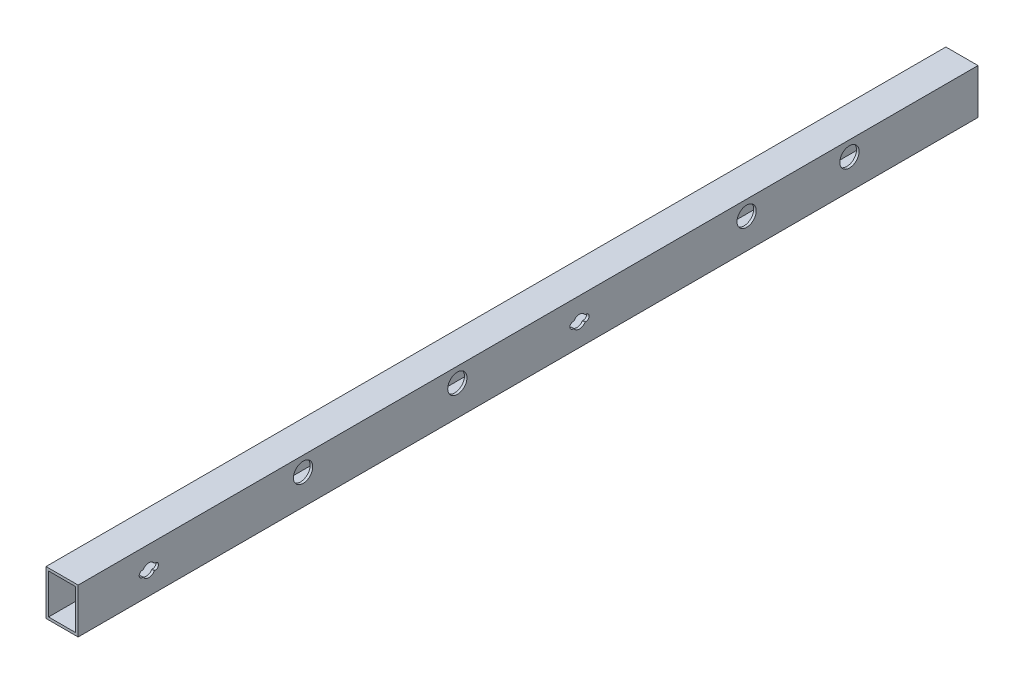
SolidWorks part; units mm, degrees
ref_plane "Front Plane" through (0, 0, 0) normal (0, 0, 1) x (1, 0, 0)
ref_plane "Top Plane" through (0, 0, 0) normal (0, 1, 0) x (1, 0, 0)
ref_plane "Right Plane" through (0, 0, 0) normal (1, 0, 0) x (0, 0, -1)
sketch "Sketch1" plane through (0, 0, 0) normal (0, 0, 1) x (1, 0, 0)
  line L1 (0, 0) -> (50, 0)
  line L2 (0, 0) -> (0, -70)
  line L3 (0, -70) -> (50, -70)
  line L4 (50, 0) -> (50, -70)
  line L5 (4, -4) -> (46, -4)
  line L6 (4, -4) -> (4, -66)
  line L7 (4, -66) -> (46, -66)
  line L8 (46, -4) -> (46, -66)
  dimension "D1" = 70
  dimension "D2" = 50
  dimension "D3" = 4
  dimension "D4" = 4
  dimension "D5" = 4
  dimension "D6" = 4
extrude "Boss-Extrude2" add sketch "Sketch1" along normal blind 1400
sketch "Sketch2" plane through (50, 0, 0) normal (1, 0, 0) x (0, 0, -1)
  line L0 (-1400, -70) -> (-1400, 0) construction
  line L1 (-1400, 0) -> (0, 0) construction
  line L2 (-1281.3397, -30) -> (-1280, -30)
  line L3 (-1300, -35) -> (-1280, -35) construction
  line L4 (-1300, -30) -> (-1298.6603, -30)
  line L5 (-1300, -40) -> (-1298.6603, -40)
  line L6 (-1400, -70) -> (0, -70) construction
  line L7 (-1281.3397, -40) -> (-1280, -40)
  line L8 (-611.3397, -30) -> (-610, -30)
  line L9 (-630, -35) -> (-610, -35) construction
  line L10 (-630, -30) -> (-628.6603, -30)
  line L11 (-630, -40) -> (-628.6603, -40)
  line L12 (-611.3397, -40) -> (-610, -40)
  circle A0 centre (-1050, -23) radius 15
  circle A1 centre (-200, -23) radius 15
  circle A2 centre (-810, -23) radius 15
  circle A3 centre (-360, -23) radius 15
  arc A6 (-1300, -30) -> (-1300, -40) centre (-1300, -35) ccw
  arc A7 (-1280, -40) -> (-1280, -30) centre (-1280, -35) ccw
  arc A8 (-1281.3397, -30) -> (-1298.6603, -30) centre (-1290, -35) ccw
  arc A9 (-1298.6603, -40) -> (-1281.3397, -40) centre (-1290, -35) ccw
  arc A10 (-630, -30) -> (-630, -40) centre (-630, -35) ccw
  arc A11 (-610, -40) -> (-610, -30) centre (-610, -35) ccw
  arc A12 (-611.3397, -30) -> (-628.6603, -30) centre (-620, -35) ccw
  arc A13 (-628.6603, -40) -> (-611.3397, -40) centre (-620, -35) ccw
  point P16 (-1290, -35)
  point P29 (-620, -35)
  point P36 (0, 0)
  point P39 (0, 0)
  point P41 (-620, -30)
  point P42 (-639.7901, -35.2984)
  point P43 (0, 0)
  point P44 (-620, -35)
  point P45 (-621.3397, -40)
  point P46 (-621.3397, -30)
  point P47 (0, 0)
  point P48 (-620, -30)
  point P49 (-620, -35)
  point P50 (-640, -35)
  point P51 (-640, -35)
  point P52 (-640, -35)
  point P53 (0, 0)
  point P54 (-620, -35)
  dimension "D1" = 30
  dimension "D2" = 30
  dimension "D3" = 30
  dimension "D4" = 30
  dimension "D12" = 5
  dimension "D16" = 20
  dimension "D19" = 5
  dimension "D11" = 5
  dimension "D24" = 20
  dimension "D27" = 5
  dimension "D5" = 350
  dimension "D6" = 240
  dimension "D7" = 450
  dimension "D8" = 160
  dimension "D9" = 23
  dimension "D10" = 35
  dimension "D13" = 20
  dimension "D15" = 100
  dimension "D17" = 5
  dimension "D18" = 5
  dimension "D20" = 10
  dimension "D21" = 10
  dimension "D22" = 1.3397
  dimension "D23" = 1.3397
  dimension "D14" = 20
  dimension "D25" = 5
  dimension "D26" = 5
  dimension "D28" = 10
  dimension "D29" = 10
  dimension "D30" = 1.3397
  dimension "D31" = 1.3397
  dimension "D32" = 35
  dimension "D33" = 260
extrude "Cut-Extrude1" cut sketch "Sketch2" against normal through all
equation "\"D4@Sketch1\"=\"D3@Sketch1\""
equation "\"D5@Sketch1\"=\"D3@Sketch1\""
equation "\"D2@Sketch2\"=\"D1@Sketch2\""
